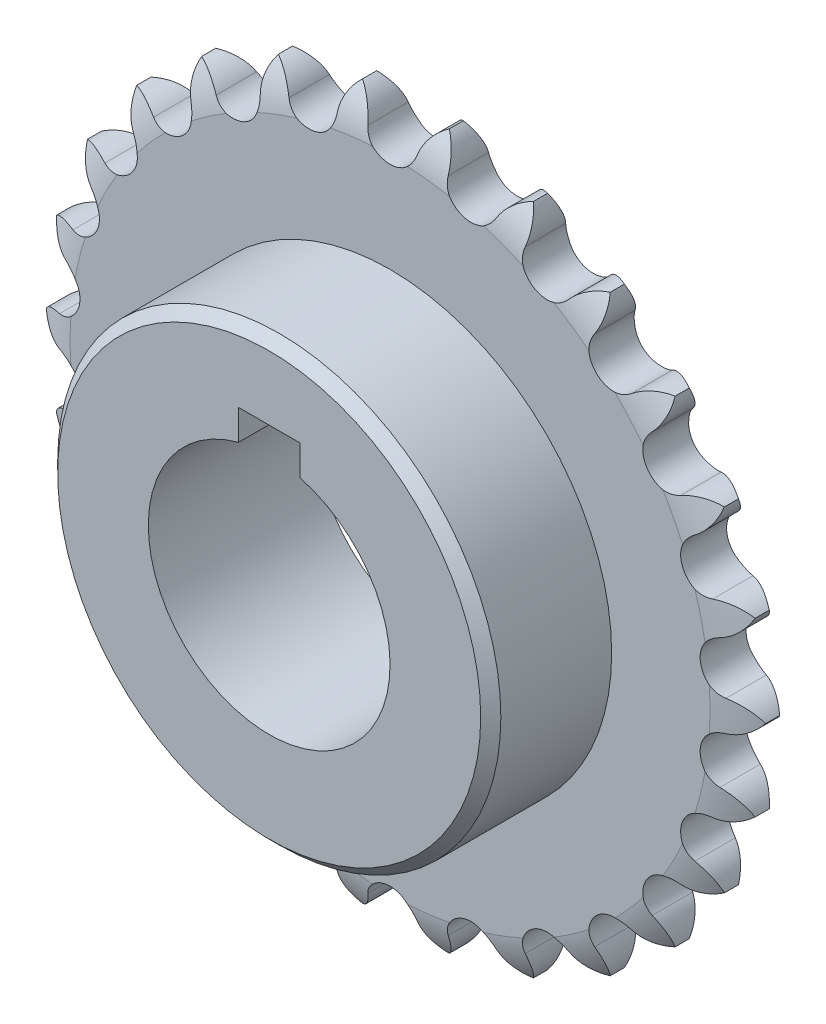
SolidWorks part; units mm, degrees
ref_plane "Front Plane" through (0, 0, 0) normal (0, 0, 1) x (1, 0, 0)
ref_plane "Top Plane" through (0, 0, 0) normal (0, 1, 0) x (1, 0, 0)
ref_plane "Right Plane" through (0, 0, 0) normal (1, 0, 0) x (0, 0, -1)
sketch "Sketch1" plane through (0, 0, 0) normal (0, 0, 1) x (1, 0, 0)
  line L0 (0, 0) -> (0, 56.7055) construction
  line L1 (0, 0) -> (9.6217, 51.1475) construction
  line L2 (0, 0) -> (9.6217, 51.1475) construction
  line L3 (0, 0) -> (21.5825, 47.3586) construction
  circle A0 centre (0, 0) radius 19.05
  circle A1 centre (0, 0) radius 49.2633 construction
  circle A2 centre (0, 0) radius 52.0446 construction
  circle A3 centre (0, 0) radius 53.2892 construction
  circle A4 centre (0, 0) radius 56.7055 construction
  arc A5 (3.9297, 52.4145) -> (-3.9297, 52.4145) centre (0, 53.2892) cw
  arc A6 (3.9297, 52.4145) -> (6.8687, 56.288) centre (9.6217, 51.1475) cw
  arc A7 (-3.9297, 52.4145) -> (-6.8687, 56.288) centre (-9.6217, 51.1475) ccw
  arc A8 (8.7281, 51.8318) -> (6.8015, 56.2961) centre (2.8983, 51.9638) ccw
  arc A9 (16.3591, 49.951) -> (8.7281, 51.8318) centre (12.7529, 51.7407) cw
  arc A10 (16.3591, 49.951) -> (20.1397, 53.0086) centre (21.5825, 47.3586) cw
  arc A11 (20.8786, 48.2369) -> (20.0764, 53.0326) centre (15.2499, 49.7602) ccw
  arc A12 (27.8378, 44.5845) -> (20.8786, 48.2369) centre (24.7647, 47.1852) cw
  arc A13 (27.8378, 44.5845) -> (32.2402, 46.6485) centre (32.289, 40.8174) cw
  arc A14 (31.8158, 41.8387) -> (32.1845, 46.6869) centre (26.7151, 44.6648) ccw
  arc A15 (37.6987, 36.6269) -> (31.8158, 41.8387) centre (35.3373, 39.8875) cw
  arc A16 (37.6987, 36.6269) -> (42.4671, 37.5774) centre (41.119, 31.9041) cw
  arc A17 (40.9039, 33.0089) -> (42.4222, 37.628) centre (36.6278, 36.9736) ccw
  arc A18 (45.3686, 26.5407) -> (40.9039, 33.0089) centre (43.8562, 30.2717) cw
  arc A19 (45.3686, 26.5407) -> (50.2259, 26.3224) centre (47.5593, 21.1366) cw
  arc A20 (47.6149, 22.2608) -> (50.1945, 26.3823) centre (44.4118, 27.1336) ccw
  arc A21 (50.4019, 14.9121) -> (47.6149, 22.2608) centre (49.8263, 18.8966) cw
  arc A22 (50.4019, 14.9121) -> (55.0658, 13.5376) centre (51.2356, 9.1407) cw
  arc A23 (51.5586, 10.2189) -> (55.0496, 13.6034) centre (49.6148, 15.7167) ccw
  arc A24 (52.506, 2.4168) -> (51.5586, 10.2189) centre (52.9007, 6.4233) cw
  arc A25 (52.506, 2.4168) -> (56.7055, -0.0338) centre (51.9343, -3.3864) cw
  arc A26 (52.506, -2.4168) -> (56.7055, 0.0338) centre (51.9343, 3.3864) ccw
  arc A27 (51.5586, -10.2189) -> (52.506, -2.4168) centre (52.9007, -6.4233) cw
  arc A28 (51.5586, -10.2189) -> (55.0496, -13.6034) centre (49.6148, -15.7167) cw
  arc A29 (50.4019, -14.9121) -> (55.0658, -13.5376) centre (51.2356, -9.1407) ccw
  arc A30 (47.6149, -22.2608) -> (50.4019, -14.9121) centre (49.8263, -18.8966) cw
  arc A31 (47.6149, -22.2608) -> (50.1945, -26.3823) centre (44.4118, -27.1336) cw
  arc A32 (45.3686, -26.5407) -> (50.2259, -26.3224) centre (47.5593, -21.1366) ccw
  arc A33 (40.9039, -33.0089) -> (45.3686, -26.5407) centre (43.8562, -30.2717) cw
  arc A34 (40.9039, -33.0089) -> (42.4222, -37.628) centre (36.6278, -36.9736) cw
  arc A35 (37.6987, -36.6269) -> (42.4671, -37.5774) centre (41.119, -31.9041) ccw
  arc A36 (31.8158, -41.8387) -> (37.6987, -36.6269) centre (35.3373, -39.8875) cw
  arc A37 (31.8158, -41.8387) -> (32.1845, -46.6869) centre (26.7151, -44.6648) cw
  arc A38 (27.8378, -44.5845) -> (32.2402, -46.6485) centre (32.289, -40.8174) ccw
  arc A39 (20.8786, -48.2369) -> (27.8378, -44.5845) centre (24.7647, -47.1852) cw
  arc A40 (20.8786, -48.2369) -> (20.0764, -53.0326) centre (15.2499, -49.7602) cw
  arc A41 (16.3591, -49.951) -> (20.1397, -53.0086) centre (21.5825, -47.3586) ccw
  arc A42 (8.7281, -51.8318) -> (16.3591, -49.951) centre (12.7529, -51.7407) cw
  arc A43 (8.7281, -51.8318) -> (6.8015, -56.2961) centre (2.8983, -51.9638) cw
  arc A44 (3.9297, -52.4145) -> (6.8687, -56.288) centre (9.6217, -51.1475) ccw
  arc A45 (-3.9297, -52.4145) -> (3.9297, -52.4145) centre (0, -53.2892) cw
  arc A46 (-3.9297, -52.4145) -> (-6.8687, -56.288) centre (-9.6217, -51.1475) cw
  arc A47 (-8.7281, -51.8318) -> (-6.8015, -56.2961) centre (-2.8983, -51.9638) ccw
  arc A48 (-16.3591, -49.951) -> (-8.7281, -51.8318) centre (-12.7529, -51.7407) cw
  arc A49 (-16.3591, -49.951) -> (-20.1397, -53.0086) centre (-21.5825, -47.3586) cw
  arc A50 (-20.8786, -48.2369) -> (-20.0764, -53.0326) centre (-15.2499, -49.7602) ccw
  arc A51 (-27.8378, -44.5845) -> (-20.8786, -48.2369) centre (-24.7647, -47.1852) cw
  arc A52 (-27.8378, -44.5845) -> (-32.2402, -46.6485) centre (-32.289, -40.8174) cw
  arc A53 (-31.8158, -41.8387) -> (-32.1845, -46.6869) centre (-26.7151, -44.6648) ccw
  arc A54 (-37.6987, -36.6269) -> (-31.8158, -41.8387) centre (-35.3373, -39.8875) cw
  arc A55 (-37.6987, -36.6269) -> (-42.4671, -37.5774) centre (-41.119, -31.9041) cw
  arc A56 (-40.9039, -33.0089) -> (-42.4222, -37.628) centre (-36.6278, -36.9736) ccw
  arc A57 (-45.3686, -26.5407) -> (-40.9039, -33.0089) centre (-43.8562, -30.2717) cw
  arc A58 (-45.3686, -26.5407) -> (-50.2259, -26.3224) centre (-47.5593, -21.1366) cw
  arc A59 (-47.6149, -22.2608) -> (-50.1945, -26.3823) centre (-44.4118, -27.1336) ccw
  arc A60 (-50.4019, -14.9121) -> (-47.6149, -22.2608) centre (-49.8263, -18.8966) cw
  arc A61 (-50.4019, -14.9121) -> (-55.0658, -13.5376) centre (-51.2356, -9.1407) cw
  arc A62 (-51.5586, -10.2189) -> (-55.0496, -13.6034) centre (-49.6148, -15.7167) ccw
  arc A63 (-52.506, -2.4168) -> (-51.5586, -10.2189) centre (-52.9007, -6.4233) cw
  arc A64 (-52.506, -2.4168) -> (-56.7055, 0.0338) centre (-51.9343, 3.3864) cw
  arc A65 (-52.506, 2.4168) -> (-56.7055, -0.0338) centre (-51.9343, -3.3864) ccw
  arc A66 (-51.5586, 10.2189) -> (-52.506, 2.4168) centre (-52.9007, 6.4233) cw
  arc A67 (-51.5586, 10.2189) -> (-55.0496, 13.6034) centre (-49.6148, 15.7167) cw
  arc A68 (-50.4019, 14.9121) -> (-55.0658, 13.5376) centre (-51.2356, 9.1407) ccw
  arc A69 (-47.6149, 22.2608) -> (-50.4019, 14.9121) centre (-49.8263, 18.8966) cw
  arc A70 (-47.6149, 22.2608) -> (-50.1945, 26.3823) centre (-44.4118, 27.1336) cw
  arc A71 (-45.3686, 26.5407) -> (-50.2259, 26.3224) centre (-47.5593, 21.1366) ccw
  arc A72 (-40.9039, 33.0089) -> (-45.3686, 26.5407) centre (-43.8562, 30.2717) cw
  arc A73 (-40.9039, 33.0089) -> (-42.4222, 37.628) centre (-36.6278, 36.9736) cw
  arc A74 (-37.6987, 36.6269) -> (-42.4671, 37.5774) centre (-41.119, 31.9041) ccw
  arc A75 (-31.8158, 41.8387) -> (-37.6987, 36.6269) centre (-35.3373, 39.8875) cw
  arc A76 (-31.8158, 41.8387) -> (-32.1845, 46.6869) centre (-26.7151, 44.6648) cw
  arc A77 (-27.8378, 44.5845) -> (-32.2402, 46.6485) centre (-32.289, 40.8174) ccw
  arc A78 (-20.8786, 48.2369) -> (-27.8378, 44.5845) centre (-24.7647, 47.1852) cw
  arc A79 (-20.8786, 48.2369) -> (-20.0764, 53.0326) centre (-15.2499, 49.7602) cw
  arc A80 (-16.3591, 49.951) -> (-20.1397, 53.0086) centre (-21.5825, 47.3586) ccw
  arc A81 (-8.7281, 51.8318) -> (-16.3591, 49.951) centre (-12.7529, 51.7407) cw
  arc A82 (-8.7281, 51.8318) -> (-6.8015, 56.2961) centre (-2.8983, 51.9638) cw
  dimension "D1" = 113.411
  dimension "D2" = 106.5784
  dimension "D3" = 104.0892
  dimension "D4" = 98.5266
  dimension "D5" = 5.8313
  dimension "D6" = 38.1
  dimension "D8" = 13.846
  dimension "D7" = 26
extrude "Boss-Extrude1" add sketch "Sketch1" along normal mid plane 7.231 contours A82 A81 A80 A79 A78 A77 A76 A75 A74 A73 A72 A71 A70 A69 A68 A67 A66 A65 A64 A63 A62 A61 A60 A59 A58 A57 A56 A55 A54 A53 A52 A51 A50 A49 A48 A47 A46 A45 A44 A43 A42 A41 A40 A39 A38 A37 A36 A35 A34 A33 A32 region at (6.2397, 53.6946, 0)
sketch "Sketch2" plane through (0, 0, 0) normal (1, 0, 0) x (0, 0, -1)
  line L1 (-3.6155, 19.05) -> (-22.6655, 19.05)
  line L2 (-3.6155, 19.05) -> (-3.6155, 34.925)
  line L3 (-3.6155, 34.925) -> (-22.6655, 34.925)
  line L4 (-22.6655, 19.05) -> (-22.6655, 34.925)
  line L5 (0, 0) -> (-78.0193, 0) construction
  line L6 (-3.6155, 37.5868) -> (-3.6155, 33.0089) construction
  dimension "D1" = 38.1
  dimension "D2" = 69.85
  dimension "D3" = 19.05
revolve "Revolve1" add sketch "Sketch2" angle 360 about L5
sketch "Sketch3" plane through (0, 0, 22.6655) normal (0, 0, 1) x (1, 0, 0)
  line L0 (0, 0) -> (0, 23.2292) construction
  line L2 (-4.825, 18.4288) -> (4.825, 18.4288)
  line L3 (-4.825, 18.4288) -> (-4.825, 23.1888)
  line L4 (-4.825, 23.1888) -> (4.825, 23.1888)
  line L5 (4.825, 18.4288) -> (4.825, 23.1888)
  circle A1 centre (0, 0) radius 19.05 construction
  dimension "D1" = 9.65
  dimension "D2" = 4.76
extrude "Cut-Extrude1" cut sketch "Sketch3" against normal through all
sketch "Sketch4" plane through (0, 0, 0) normal (1, 0, 0) x (0, 0, -1)
  line L0 (0, 0) -> (-64.3119, 0) construction
  line L1 (-3.6155, 50.42) -> (-12.3309, 50.42)
  line L2 (-12.3309, 50.42) -> (-12.3309, 56.89)
  line L3 (-12.3309, 56.89) -> (-0.954, 56.89)
  line L4 (0, 35.4921) -> (0, 64.3319) construction
  line L5 (-3.6155, 52.9981) -> (-3.6155, 48.2369) construction
  arc A0 (-0.954, 56.89) -> (-3.6155, 50.42) centre (9.006, 49.0105) ccw
  dimension "D1" = 50.42
  dimension "D3" = 12.7
  dimension "D2" = 56.89
revolve "Cut-Revolve1" cut sketch "Sketch4" angle 360 about L0
mirror "Mirror1" about plane through (0, 0, 0) normal (0, 0, 1) of "Cut-Revolve1"
chamfer "Chamfer2" distance 1.5875 angle 45 1 edges at (-34.925, 0, 22.6655)
ref_axis "Axis1" through (0, 0, 22.6655) along (0, 0, -1)
sketch "草图1" plane through (0, 0, -3.6155) normal (0, 0, -1) x (-1, 0, 0)
  circle A0 centre (0, 0) radius 53.848
scale "缩放比例1" scale about centroid uniform scaling yes scale factor 0.5
scale "缩放比例2" scale about centroid uniform scaling yes scale factor 2
scale "缩放比例3" scale about centroid uniform scaling yes scale factor 0.111111
